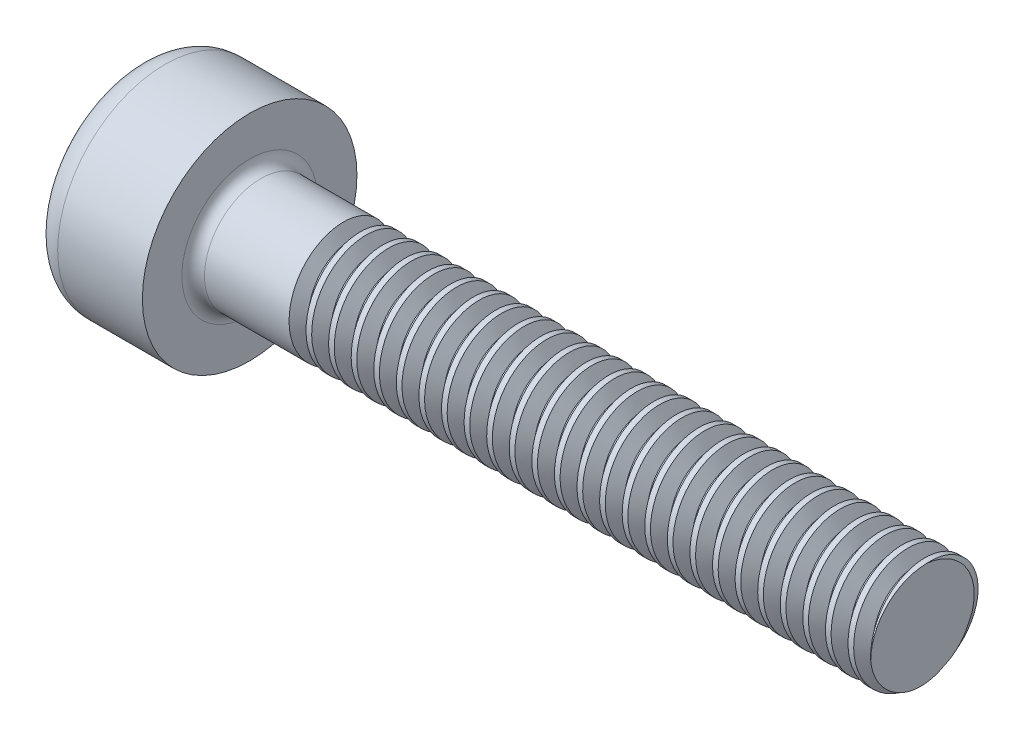
SolidWorks part; units mm, degrees
ref_plane "Спереди" through (0, 0, 0) normal (0, 0, 1) x (1, 0, 0)
ref_plane "Сверху" through (0, 0, 0) normal (0, 1, 0) x (1, 0, 0)
ref_plane "Справа" through (0, 0, 0) normal (1, 0, 0) x (0, 0, -1)
sketch "Эскиз1" plane through (0, 0, 0) normal (0, 0, 1) x (1, 0, 0)
  line L0 (22.1989, 0) -> (14, 0) construction
  line L1 (0, 16.1035) -> (0, -19.7496) construction
  line L2 (0, 0) -> (14, 0)
  line L3 (0, 0) -> (0, 1.9)
  line L4 (0, 1.9) -> (2, 1.9)
  line L5 (2, 1.9) -> (2, 1)
  line L6 (2, 1) -> (14, 1)
  line L7 (14, 1) -> (14, 0)
  dimension "D1" = 3.8
  dimension "D2" = 2
  dimension "D3" = 12
  dimension "D4" = 2
revolve "Повернуть1" add sketch "Эскиз1" angle 360 about L0
thread "Резьба1" pitch 0.4 method cut profile "Профиль резьбы2" start angle 0, offset 1.5, length 0, pitch 0.4, diameter 2
ref_plane "Плоскость2" through (3.5, 0, -1) normal (0, 1, 0) x (0, 0, 1)
sketch "Профиль резьбы2" plane through (3.5, 0, -1) normal (0, 1, 0) x (0, 0, 1)
  line L0 (0, 0) -> (0, 0.4) construction
  line L1 (0, 0) -> (0.2165, 0.125)
  line L2 (0.2165, 0.125) -> (0.2165, 0.175)
  line L3 (0.2165, 0.175) -> (0, 0.3)
  line L4 (0.2165, 0.15) -> (0, 0.15) construction
  line L11 (0, 0) -> (0, 0.3)
  point P2 (0, 0)
  dimension "Pitch" = 0.4
  dimension "Profile_Angle" = 60
  dimension "Profile_Land" = 0.05
  dimension "Profile_Height" = 0.2165
sketch "Эскиз6" plane through (0, 0, 0) normal (-1, 0, 0) x (0, 0, 1)
  line L0 (0, 0) -> (-5.0338, 0) construction
  line L1 (0, 0) -> (0, 5.5177) construction
  line L3 (-0.75, 0) -> (-0.375, -0.6495)
  line L4 (-0.375, -0.6495) -> (0.375, -0.6495)
  line L5 (0.375, -0.6495) -> (0.75, 0)
  line L6 (0.75, 0) -> (0.375, 0.6495)
  line L7 (0.375, 0.6495) -> (-0.375, 0.6495)
  line L8 (-0.375, 0.6495) -> (-0.75, 0)
  dimension "D1" = 1.299
  dimension "D2" = 1.5
extrude "Вырез-Вытянуть1" cut sketch "Эскиз6" against normal blind 1 contours L3 L4 L5 L6 L7 L8
extrude "Вырез-Вытянуть2" cut sketch "Эскиз6<3>" against normal blind 2 draft 60 from offset 1 offset against normal yes
sketch "Эскиз6<3>" plane through (0, 0, 0) normal (-1, 0, 0) x (0, 0, 1) same geometry as "Эскиз6"
fillet "Скругление2" radius 0.5 1 edges at (0, 0, -1.9)
fillet "Скругление3" radius 0.2 1 edges at (2, 0, -1)
